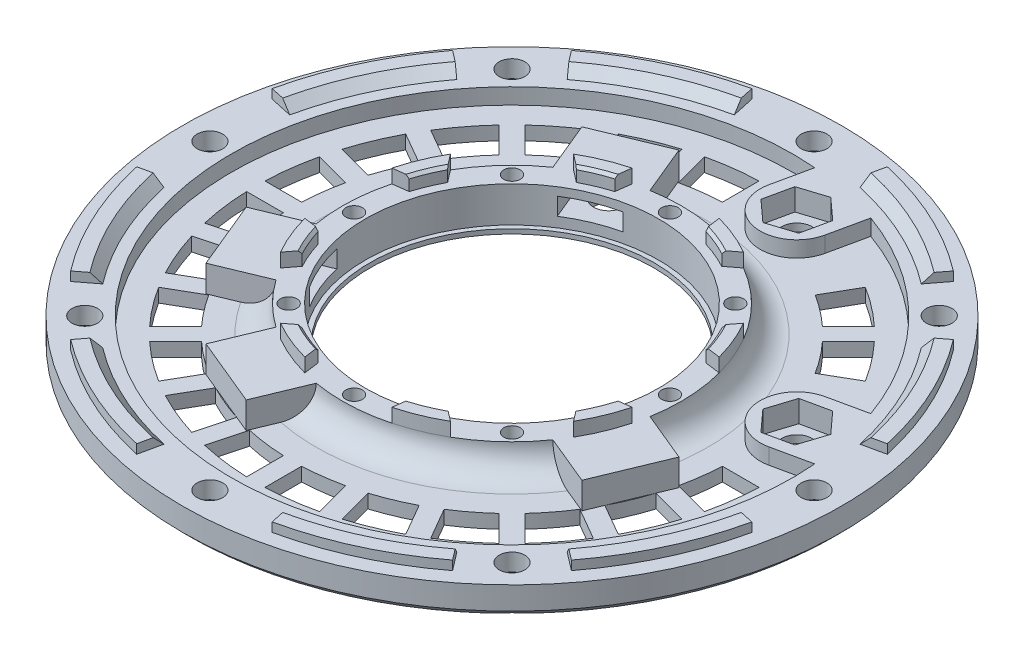
SolidWorks part; units mm, degrees
ref_plane "Front Plane" through (0, 0, 0) normal (0, 0, 1) x (1, 0, 0)
ref_plane "Top Plane" through (0, 0, 0) normal (0, 1, 0) x (1, 0, 0)
ref_plane "Right Plane" through (0, 0, 0) normal (1, 0, 0) x (0, 0, -1)
sketch "Sketch1" plane through (0, 0, 0) normal (0, 1, 0) x (1, 0, 0)
  circle A0 centre (0, 0) radius 16.025
  circle A1 centre (0, 0) radius 36
  dimension "D1" = 32.05
  dimension "D2" = 72
extrude "Boss-Extrude1" add sketch "Sketch1" along normal blind 1
sketch "Sketch2" plane through (0, 0, 0) normal (0, -1, 0) x (1, 0, 0)
  circle A0 centre (0, 0) radius 17.25 construction
  circle A1 centre (0, 0) radius 18.5 construction
  circle A2 centre (0, 0) radius 18.5
  circle A3 centre (0, 0) radius 16.025 construction
  circle A4 centre (0, 0) radius 16.025
  arc A5 (-1.2, 18.461) -> (-4.705, 17.8917) centre (0, 0) ccw construction
  point P3 (0, -17.25)
extrude "Boss-Extrude2" add sketch "Sketch2" against normal offset from surface (3.9 mm away) 3.9 up to face at (0, 0, 36)
fillet "Fillet1" radius 2.9 1 edges at (0, 1, 18.5)
sketch "Sketch4" plane through (0, 0, 0) normal (0, 1, 0) x (1, 0, 0)
  circle A0 centre (0, 0) radius 15.525
  circle A1 centre (0, 0) radius 36
  circle A2 centre (0, 0) radius 36
  circle A3 centre (0, 0) radius 16.025 construction
  dimension "D2" = 0.5
  dimension "D1" = 0
extrude "Boss-Extrude3" add sketch "Sketch4" against normal blind 0.5
sketch "Sketch5" plane through (0, 1, 0) normal (0, 1, 0) x (1, 0, 0)
  line L0 (27.99, -0.75) -> (19.9859, -0.75) construction
  line L1 (19.9859, 0.75) -> (27.99, 0.75) construction
  line L2 (27.99, -0.75) -> (19.9859, -0.75) construction
  line L3 (19.9859, 0.75) -> (27.99, 0.75) construction
  line L4 (0, 0) -> (36, 0) construction
  line L5 (0, 0) -> (34.7733, 9.3175) construction
  line L6 (34.7733, 9.3175) -> (36, 0) construction
  line L7 (0, 0) -> (35.3867, 4.6587) construction
  line L8 (27.99, 1) -> (23.9792, 1)
  line L9 (27.295, 6.2784) -> (23.4209, 5.2403)
  line L10 (27.99, -1) -> (23.9792, -1)
  line L11 (27.295, -6.2784) -> (23.4209, -5.2403)
  line L12 (26.7774, -8.2103) -> (22.9033, -7.1722)
  line L13 (24.74, -13.129) -> (21.2666, -11.1236)
  line L14 (23.74, -14.861) -> (20.2666, -12.8556)
  line L15 (20.499, -19.0848) -> (17.6629, -16.2487)
  line L16 (19.0848, -20.499) -> (16.2487, -17.6629)
  line L17 (14.861, -23.74) -> (12.8556, -20.2666)
  line L18 (13.129, -24.74) -> (11.1236, -21.2666)
  line L19 (8.2103, -26.7774) -> (7.1722, -22.9033)
  line L20 (6.2784, -27.295) -> (5.2403, -23.4209)
  line L21 (1, -27.99) -> (1, -23.9792)
  line L22 (-1, -27.99) -> (-1, -23.9792)
  line L23 (-6.2784, -27.295) -> (-5.2403, -23.4209)
  line L24 (-8.2103, -26.7774) -> (-7.1722, -22.9033)
  line L25 (-13.129, -24.74) -> (-11.1236, -21.2666)
  line L26 (-14.861, -23.74) -> (-12.8556, -20.2666)
  line L27 (-19.0848, -20.499) -> (-16.2487, -17.6629)
  line L28 (-20.499, -19.0848) -> (-17.6629, -16.2487)
  line L29 (-23.74, -14.861) -> (-20.2666, -12.8556)
  line L30 (-24.74, -13.129) -> (-21.2666, -11.1236)
  line L31 (-26.7774, -8.2103) -> (-22.9033, -7.1722)
  line L32 (-27.295, -6.2784) -> (-23.4209, -5.2403)
  line L33 (-27.99, -1) -> (-23.9792, -1)
  line L34 (-27.99, 1) -> (-23.9792, 1)
  line L35 (-27.295, 6.2784) -> (-23.4209, 5.2403)
  line L36 (-26.7774, 8.2103) -> (-22.9033, 7.1722)
  line L37 (-24.74, 13.129) -> (-21.2666, 11.1236)
  line L38 (-23.74, 14.861) -> (-20.2666, 12.8556)
  line L39 (-20.499, 19.0848) -> (-17.6629, 16.2487)
  line L40 (-19.0848, 20.499) -> (-16.2487, 17.6629)
  line L41 (-14.861, 23.74) -> (-12.8556, 20.2666)
  line L42 (-13.129, 24.74) -> (-11.1236, 21.2666)
  line L43 (-8.2103, 26.7774) -> (-7.1722, 22.9033)
  line L44 (-6.2784, 27.295) -> (-5.2403, 23.4209)
  line L45 (-1, 27.99) -> (-1, 23.9792)
  line L46 (1, 27.99) -> (1, 23.9792)
  line L47 (6.2784, 27.295) -> (5.2403, 23.4209)
  line L48 (8.2103, 26.7774) -> (7.1722, 22.9033)
  line L49 (13.129, 24.74) -> (11.1236, 21.2666)
  line L50 (14.861, 23.74) -> (12.8556, 20.2666)
  line L51 (19.0848, 20.499) -> (16.2487, 17.6629)
  line L52 (20.499, 19.0848) -> (17.6629, 16.2487)
  line L53 (23.74, 14.861) -> (20.2666, 12.8556)
  line L54 (24.74, 13.129) -> (21.2666, 11.1236)
  line L55 (26.7774, 8.2103) -> (22.9033, 7.1722)
  line L56 (0, 0) -> (23.9792, 1) construction
  circle A0 centre (0, 0) radius 24 construction
  circle A2 centre (0, 0) radius 36 construction
  arc A3 (23.9792, 1) -> (23.4209, 5.2403) centre (0, 0) ccw
  arc A4 (27.99, 1) -> (27.295, 6.2784) centre (0, 0) ccw
  arc A5 (27.295, -6.2784) -> (27.99, -1) centre (0, 0) ccw
  arc A6 (23.4209, -5.2403) -> (23.9792, -1) centre (0, 0) ccw
  arc A7 (24.74, -13.129) -> (26.7774, -8.2103) centre (0, 0) ccw
  arc A8 (21.2666, -11.1236) -> (22.9033, -7.1722) centre (0, 0) ccw
  arc A9 (20.499, -19.0848) -> (23.74, -14.861) centre (0, 0) ccw
  arc A10 (17.6629, -16.2487) -> (20.2666, -12.8556) centre (0, 0) ccw
  arc A11 (14.861, -23.74) -> (19.0848, -20.499) centre (0, 0) ccw
  arc A12 (12.8556, -20.2666) -> (16.2487, -17.6629) centre (0, 0) ccw
  arc A13 (8.2103, -26.7774) -> (13.129, -24.74) centre (0, 0) ccw
  arc A14 (7.1722, -22.9033) -> (11.1236, -21.2666) centre (0, 0) ccw
  arc A15 (1, -27.99) -> (6.2784, -27.295) centre (0, 0) ccw
  arc A16 (1, -23.9792) -> (5.2403, -23.4209) centre (0, 0) ccw
  arc A17 (-6.2784, -27.295) -> (-1, -27.99) centre (0, 0) ccw
  arc A18 (-5.2403, -23.4209) -> (-1, -23.9792) centre (0, 0) ccw
  arc A19 (-13.129, -24.74) -> (-8.2103, -26.7774) centre (0, 0) ccw
  arc A20 (-11.1236, -21.2666) -> (-7.1722, -22.9033) centre (0, 0) ccw
  arc A21 (-19.0848, -20.499) -> (-14.861, -23.74) centre (0, 0) ccw
  arc A22 (-16.2487, -17.6629) -> (-12.8556, -20.2666) centre (0, 0) ccw
  arc A23 (-23.74, -14.861) -> (-20.499, -19.0848) centre (0, 0) ccw
  arc A24 (-20.2666, -12.8556) -> (-17.6629, -16.2487) centre (0, 0) ccw
  arc A25 (-26.7774, -8.2103) -> (-24.74, -13.129) centre (0, 0) ccw
  arc A26 (-22.9033, -7.1722) -> (-21.2666, -11.1236) centre (0, 0) ccw
  arc A27 (-27.99, -1) -> (-27.295, -6.2784) centre (0, 0) ccw
  arc A28 (-23.9792, -1) -> (-23.4209, -5.2403) centre (0, 0) ccw
  arc A29 (-27.295, 6.2784) -> (-27.99, 1) centre (0, 0) ccw
  arc A30 (-23.4209, 5.2403) -> (-23.9792, 1) centre (0, 0) ccw
  arc A31 (-24.74, 13.129) -> (-26.7774, 8.2103) centre (0, 0) ccw
  arc A32 (-21.2666, 11.1236) -> (-22.9033, 7.1722) centre (0, 0) ccw
  arc A33 (-20.499, 19.0848) -> (-23.74, 14.861) centre (0, 0) ccw
  arc A34 (-17.6629, 16.2487) -> (-20.2666, 12.8556) centre (0, 0) ccw
  arc A35 (-14.861, 23.74) -> (-19.0848, 20.499) centre (0, 0) ccw
  arc A36 (-12.8556, 20.2666) -> (-16.2487, 17.6629) centre (0, 0) ccw
  arc A37 (-8.2103, 26.7774) -> (-13.129, 24.74) centre (0, 0) ccw
  arc A38 (-7.1722, 22.9033) -> (-11.1236, 21.2666) centre (0, 0) ccw
  arc A39 (-1, 27.99) -> (-6.2784, 27.295) centre (0, 0) ccw
  arc A40 (-1, 23.9792) -> (-5.2403, 23.4209) centre (0, 0) ccw
  arc A41 (6.2784, 27.295) -> (1, 27.99) centre (0, 0) ccw
  arc A42 (5.2403, 23.4209) -> (1, 23.9792) centre (0, 0) ccw
  arc A43 (13.129, 24.74) -> (8.2103, 26.7774) centre (0, 0) ccw
  arc A44 (11.1236, 21.2666) -> (7.1722, 22.9033) centre (0, 0) ccw
  arc A45 (19.0848, 20.499) -> (14.861, 23.74) centre (0, 0) ccw
  arc A46 (16.2487, 17.6629) -> (12.8556, 20.2666) centre (0, 0) ccw
  arc A47 (23.74, 14.861) -> (20.499, 19.0848) centre (0, 0) ccw
  arc A48 (20.2666, 12.8556) -> (17.6629, 16.2487) centre (0, 0) ccw
  arc A49 (26.7774, 8.2103) -> (24.74, 13.129) centre (0, 0) ccw
  arc A50 (22.9033, 7.1722) -> (21.2666, 11.1236) centre (0, 0) ccw
  dimension "D1" = 15
  dimension "D2" = 1
  dimension "D4" = 24
  dimension "D3" = 24
extrude "Cut-Extrude1" cut sketch "Sketch5" against normal through all both and the other way through all
sketch "Sketch7" plane through (0, 3.9, 0) normal (0, 1, 0) x (1, 0, 0)
  line L0 (0, 0) -> (0, 17.25) construction
  circle A0 centre (0, 17.25) radius 0.9
  circle A1 centre (12.1976, 12.1976) radius 0.9
  circle A2 centre (17.25, 0) radius 0.9
  circle A3 centre (12.1976, -12.1976) radius 0.9
  circle A4 centre (0, -17.25) radius 0.9
  circle A5 centre (-12.1976, -12.1976) radius 0.9
  circle A6 centre (-17.25, 0) radius 0.9
  circle A7 centre (-12.1976, 12.1976) radius 0.9
  point P21 (0, 0)
  dimension "D1" = 1.8
  dimension "D2" = 8
extrude "Cut-Extrude2" cut sketch "Sketch7" against normal through all
sketch "Sketch8" plane through (0, 1, 0) normal (0, 1, 0) x (1, 0, 0)
  arc A0 (-30.6392, -0.8144) -> (-29.9521, -6.5032) centre (0, 0) ccw construction
  arc A1 (-30.6392, -0.8144) -> (-29.9521, -6.5032) centre (0, 0) ccw construction
  arc A2 (-29.9521, 6.5032) -> (-30.6392, 0.8144) centre (0, 0) ccw construction
  arc A3 (-29.9521, 6.5032) -> (-30.6392, 0.8144) centre (0, 0) ccw construction
  circle A5 centre (0, 0) radius 30.65
  circle A6 centre (0, 0) radius 36 construction
  circle A7 centre (0, 0) radius 36
extrude "Boss-Extrude4" add sketch "Sketch8" along normal blind 1.7378
sketch "Sketch9" plane through (0, 2.7378, 0) normal (0, 1, 0) x (1, 0, 0)
  line L0 (0, 0) -> (-29.9521, 6.5032) construction
  line L1 (0, 0) -> (-29.9521, -6.5032) construction
  line L2 (-29.9521, 6.5032) -> (-29.9521, -6.5032) construction
  line L3 (-27.3707, 21.0023) -> (-23.9196, 18.3542) construction
  line L4 (0, 0) -> (0, 36) construction
  line L5 (0, 0) -> (-25.4558, 25.4558) construction
  line L6 (-24.3163, 18.6585) -> (0, 0) construction
  line L7 (-24.3163, 18.6585) -> (-28.5607, 21.9154) construction
  line L8 (-29.9521, 6.5032) -> (-35.1803, 7.6384) construction
  line L9 (-27.3521, 20.862) -> (-25.3687, 19.3401)
  line L10 (-31.2086, 14.47) -> (0, 0) construction
  line L11 (-33.5954, 7.3966) -> (-31.1523, 6.8662)
  line L12 (-7.3966, 33.5954) -> (-6.8662, 31.1523)
  line L13 (-20.862, 27.3521) -> (-19.3401, 25.3687)
  arc A0 (-29.9521, 6.5032) -> (-24.3163, 18.6585) centre (0, 0) cw construction
  arc A1 (-35.1803, 7.6384) -> (-28.5607, 21.9154) centre (0, 0) cw construction
  circle A2 centre (0, 0) radius 36 construction
  circle A3 centre (0, 0) radius 30.65 construction
  arc A4 (-27.2914, 20.9414) -> (-33.6168, 7.2989) centre (0, 0) ccw construction
  arc A5 (-31.1523, 6.8662) -> (-25.3687, 19.3401) centre (0, 0) cw
  arc A6 (-33.5954, 7.3966) -> (-27.3521, 20.862) centre (0, 0) cw
  circle A7 centre (0, 0) radius 36 construction
  arc A8 (-6.8662, 31.1523) -> (-19.3401, 25.3687) centre (0, 0) ccw
  arc A9 (-7.3966, 33.5954) -> (-20.862, 27.3521) centre (0, 0) ccw
  dimension "D2" = 0.1
  dimension "D3" = 45
  dimension "D4" = 0.1
  dimension "D1" = 2.5
extrude "Boss-Extrude5" add sketch "Sketch9" along normal blind 1
ref_axis "Axis1" through (0, -0.72, 0) along (0, 1, 0)
pattern_circular "CirPattern1" count 4 over 360 about axis through (0, -0.72, 0) along (0, 1, 0) of "Boss-Extrude5"
chamfer "Chamfer1" distance 1 angle 45 8 edges at (-28.9406, 3.7378, -13.4184) (-13.4184, 3.7378, -28.9406) (13.4184, 3.7378, -28.9406) (28.9406, 3.7378, -13.4184) (28.9406, 3.7378, 13.4184) (13.4184, 3.7378, 28.9406) (-13.4184, 3.7378, 28.9406) (-28.9406, 3.7378, 13.4184)
sketch "Sketch10" plane through (0, 2.7378, 0) normal (0, 1, 0) x (1, 0, 0)
  line L0 (0, 0) -> (0, 36) construction
  circle A0 centre (0, 0) radius 36 construction
  circle A1 centre (0, 33) radius 1.4 construction
  circle A2 centre (0, 33) radius 1.4
  circle A3 centre (23.3345, 23.3345) radius 1.4
  circle A4 centre (33, 0) radius 1.4
  circle A5 centre (23.3345, -23.3345) radius 1.4
  circle A6 centre (0, -33) radius 1.4
  circle A7 centre (-23.3345, -23.3345) radius 1.4
  circle A8 centre (-33, 0) radius 1.4
  circle A9 centre (-23.3345, 23.3345) radius 1.4
  point P26 (0, 0)
  dimension "D1" = 8
extrude "Cut-Extrude3" cut sketch "Sketch10" against normal through all both and the other way through all
chamfer "Chamfer2" distance 0.75 angle 45 1 edges at (0, -0.5, 36)
hole_wizard "CSK for M2.5 Flat Head Machine Screw1" positions "Sketch11" profile "Sketch12" countersink size "M2.5" standard "ANSI Metric" end condition through all
sketch "Sketch11" plane through (0, -0.5, 0) normal (0, -1, 0) x (-1, 0, 0)
  point P0 (0, -33)
  point P3 (23.3345, -23.3345)
  point P6 (33, 0)
  point P9 (23.3345, 23.3345)
  point P12 (0, 33)
  point P15 (-23.3345, 23.3345)
  point P18 (-33, 0)
  point P21 (-23.3345, -23.3345)
sketch "Sketch12" plane through (0, -0.5, 33) normal (1, 0, 0) x (0, 0, -1)
  line L0 (0, 0) -> (0, 4.4)
  line L1 (0, 4.4) -> (1.35, 4.4)
  line L2 (1.35, 4.4) -> (1.35, 1.4)
  line L3 (1.35, 1.4) -> (2.75, 0)
  line L5 (2.75, 0) -> (0, 0)
  line L6 (-1.35, 1.4) -> (-2.75, 0) construction
  line L11 (0, -6.35) -> (0, 107.95) construction
  dimension "Thru Hole Dia." = 2.7
  dimension "Thru Hole Depth" = 4.4
  dimension "Near C'Sink Dia." = 5.5
  dimension "Near C'Sink Angle" = 90
sketch "Sketch13" plane through (0, 3.9, 0) normal (0, 1, 0) x (1, 0, 0)
  line L0 (0, 0) -> (-7.0796, 17.0918) construction
  line L1 (0, 0) -> (0, 18.5) construction
  line L2 (-9.2808, 16.0037) -> (-7.9403, 14.9751)
  line L3 (-4.7538, 17.8788) -> (-4.9743, 16.2037)
  line L4 (4.7538, 17.8788) -> (4.9743, 16.2037)
  line L5 (9.2808, 16.0037) -> (7.9403, 14.9751)
  line L6 (16.0037, 9.2808) -> (14.9751, 7.9403)
  line L7 (17.8788, 4.7538) -> (16.2037, 4.9743)
  line L8 (17.8788, -4.7538) -> (16.2037, -4.9743)
  line L9 (16.0037, -9.2808) -> (14.9751, -7.9403)
  line L10 (9.2808, -16.0037) -> (7.9403, -14.9751)
  line L11 (4.7538, -17.8788) -> (4.9743, -16.2037)
  line L12 (-4.7538, -17.8788) -> (-4.9743, -16.2037)
  line L13 (-9.2808, -16.0037) -> (-7.9403, -14.9751)
  line L14 (-16.0037, -9.2808) -> (-14.9751, -7.9403)
  line L15 (-17.8788, -4.7538) -> (-16.2037, -4.9743)
  line L16 (-17.8788, 4.7538) -> (-16.2037, 4.9743)
  line L17 (-16.0037, 9.2808) -> (-14.9751, 7.9403)
  circle A0 centre (0, 0) radius 18.5 construction
  arc A1 (-7.9403, 14.9751) -> (-4.9743, 16.2037) centre (0, 0) cw
  arc A2 (-9.2808, 16.0037) -> (-4.7538, 17.8788) centre (0, 0) cw
  arc A3 (4.9743, 16.2037) -> (7.9403, 14.9751) centre (0, 0) cw
  arc A4 (4.7538, 17.8788) -> (9.2808, 16.0037) centre (0, 0) cw
  arc A5 (14.9751, 7.9403) -> (16.2037, 4.9743) centre (0, 0) cw
  arc A6 (16.0037, 9.2808) -> (17.8788, 4.7538) centre (0, 0) cw
  arc A7 (16.2037, -4.9743) -> (14.9751, -7.9403) centre (0, 0) cw
  arc A8 (17.8788, -4.7538) -> (16.0037, -9.2808) centre (0, 0) cw
  arc A9 (7.9403, -14.9751) -> (4.9743, -16.2037) centre (0, 0) cw
  arc A10 (9.2808, -16.0037) -> (4.7538, -17.8788) centre (0, 0) cw
  arc A11 (-4.9743, -16.2037) -> (-7.9403, -14.9751) centre (0, 0) cw
  arc A12 (-4.7538, -17.8788) -> (-9.2808, -16.0037) centre (0, 0) cw
  arc A13 (-14.9751, -7.9403) -> (-16.2037, -4.9743) centre (0, 0) cw
  arc A14 (-16.0037, -9.2808) -> (-17.8788, -4.7538) centre (0, 0) cw
  arc A15 (-16.2037, 4.9743) -> (-14.9751, 7.9403) centre (0, 0) cw
  arc A16 (-17.8788, 4.7538) -> (-16.0037, 9.2808) centre (0, 0) cw
  point P12 (-6.4865, 15.6598)
  point P20 (6.4865, 15.6598)
  point P25 (15.6598, 6.4865)
  point P30 (15.6598, -6.4865)
  point P35 (6.4865, -15.6598)
  point P40 (-6.4865, -15.6598)
  point P45 (-15.6598, -6.4865)
  point P50 (-15.6598, 6.4865)
  point P51 (0, 0)
  dimension "D1" = 22.5
  dimension "D2" = 30
  dimension "D3" = 1.55
  dimension "D4" = 4.9
  dimension "D5" = 8
extrude "Boss-Extrude6" add sketch "Sketch13" along normal blind 1.5
chamfer "Chamfer3" distance 0.3 angle 45 8 edges at (-15.6598, 5.4, -6.4865) (-15.6598, 5.4, 6.4865) (-6.4865, 5.4, 15.6598) (6.4865, 5.4, 15.6598) (15.6598, 5.4, 6.4865) (15.6598, 5.4, -6.4865) (6.4865, 5.4, -15.6598) (-6.4865, 5.4, -15.6598)
sketch "Sketch14" plane through (0, -0.5, 0) normal (0, -1, 0) x (1, 0, 0)
  line L0 (0, 0) -> (25.4558, -25.4558) construction
  line L1 (0, 0) -> (0, -36) construction
  line L6 (0, 0) -> (-22.1731, 9.1844) construction
  line L7 (0, 0) -> (-9.1844, -22.1731) construction
  circle A0 centre (0, 0) radius 36 construction
  arc A5 (-21.2666, 11.1236) -> (-22.9033, 7.1722) centre (0, 0) ccw construction
  circle A6 centre (-18.0157, 7.4623) radius 1.65
  circle A7 centre (-18.0157, 7.4623) radius 4.5 construction
  arc A8 (-11.1236, -21.2666) -> (-7.1722, -22.9033) centre (0, 0) ccw construction
  circle A9 centre (-7.4623, -18.0157) radius 1.65
  circle A10 centre (-7.4623, -18.0157) radius 4.5 construction
  circle A11 centre (18.0157, 7.4623) radius 1.65
  circle A12 centre (-7.4623, 18.0157) radius 1.65
  dimension "D2" = 3.3
  dimension "D3" = 9
  dimension "D1" = 45
sketch "Sketch15" plane through (0, 1, 0) normal (0, 1, 0) x (1, 0, 0)
  line L0 (-9.8825, 13.2519) -> (-12.8979, 20.5316)
  line L1 (-9.8825, 13.2519) -> (-2.3825, 16.3585)
  line L2 (-12.8979, 20.5316) -> (-5.3979, 23.6382)
  line L3 (-2.3825, 16.3585) -> (-5.3979, 23.6382)
  line L4 (-9.8825, 13.2519) -> (-5.3979, 23.6382) construction
  line L5 (-12.8979, 20.5316) -> (-2.3825, 16.3585) construction
  line L6 (0, 0) -> (-9.1844, 22.1731) construction
  line L7 (2.3825, 16.3585) -> (5.3979, 23.6382) [skipped]
  line L8 (2.3825, 16.3585) -> (9.8825, 13.2519) [skipped]
  line L9 (5.3979, 23.6382) -> (12.8979, 20.5316) [skipped]
  line L10 (9.8825, 13.2519) -> (12.8979, 20.5316) [skipped]
  line L11 (2.3825, 16.3585) -> (12.8979, 20.5316) construction
  line L12 (5.3979, 23.6382) -> (9.8825, 13.2519) construction
  line L13 (13.2519, 9.8825) -> (20.5316, 12.8979) [skipped]
  line L14 (13.2519, 9.8825) -> (16.3585, 2.3825) [skipped]
  line L15 (20.5316, 12.8979) -> (23.6382, 5.3979) [skipped]
  line L16 (16.3585, 2.3825) -> (23.6382, 5.3979) [skipped]
  line L17 (13.2519, 9.8825) -> (23.6382, 5.3979) construction
  line L18 (20.5316, 12.8979) -> (16.3585, 2.3825) construction
  line L19 (16.3585, -2.3825) -> (23.6382, -5.3979)
  line L20 (16.3585, -2.3825) -> (13.2519, -9.8825)
  line L21 (23.6382, -5.3979) -> (20.5316, -12.8979)
  line L22 (13.2519, -9.8825) -> (20.5316, -12.8979)
  line L23 (16.3585, -2.3825) -> (20.5316, -12.8979) construction
  line L24 (23.6382, -5.3979) -> (13.2519, -9.8825) construction
  line L25 (9.8825, -13.2519) -> (12.8979, -20.5316) [skipped]
  line L26 (9.8825, -13.2519) -> (2.3825, -16.3585) [skipped]
  line L27 (12.8979, -20.5316) -> (5.3979, -23.6382) [skipped]
  line L28 (2.3825, -16.3585) -> (5.3979, -23.6382) [skipped]
  line L29 (9.8825, -13.2519) -> (5.3979, -23.6382) construction
  line L30 (12.8979, -20.5316) -> (2.3825, -16.3585) construction
  line L31 (-2.3825, -16.3585) -> (-5.3979, -23.6382)
  line L32 (-2.3825, -16.3585) -> (-9.8825, -13.2519)
  line L33 (-5.3979, -23.6382) -> (-12.8979, -20.5316)
  line L34 (-9.8825, -13.2519) -> (-12.8979, -20.5316)
  line L35 (-2.3825, -16.3585) -> (-12.8979, -20.5316) construction
  line L36 (-5.3979, -23.6382) -> (-9.8825, -13.2519) construction
  line L37 (-13.2519, -9.8825) -> (-20.5316, -12.8979)
  line L38 (-13.2519, -9.8825) -> (-16.3585, -2.3825)
  line L39 (-20.5316, -12.8979) -> (-23.6382, -5.3979)
  line L40 (-16.3585, -2.3825) -> (-23.6382, -5.3979)
  line L41 (-13.2519, -9.8825) -> (-23.6382, -5.3979) construction
  line L42 (-20.5316, -12.8979) -> (-16.3585, -2.3825) construction
  line L43 (-16.3585, 2.3825) -> (-23.6382, 5.3979) [skipped]
  line L44 (-16.3585, 2.3825) -> (-13.2519, 9.8825) [skipped]
  line L45 (-23.6382, 5.3979) -> (-20.5316, 12.8979) [skipped]
  line L46 (-13.2519, 9.8825) -> (-20.5316, 12.8979) [skipped]
  line L47 (-16.3585, 2.3825) -> (-20.5316, 12.8979) construction
  line L48 (-23.6382, 5.3979) -> (-13.2519, 9.8825) construction
  line L49 (0, 0) -> (-9.1844, 22.1731) construction
  arc A1 (-7.1722, 22.9033) -> (-11.1236, 21.2666) centre (0, 0) ccw construction
  circle A2 centre (0, 0) radius 16.025 construction
  point P1 (-7.6402, 18.445)
  point P9 (7.6402, 18.445)
  point P18 (18.445, 7.6402)
  point P23 (18.445, -7.6402)
  point P28 (7.6402, -18.445)
  point P33 (-7.6402, -18.445)
  point P38 (-18.445, -7.6402)
  point P43 (-18.445, 7.6402)
  point P48 (0, 0)
  dimension "D1" = 7.5
  dimension "D2" = 8
extrude "Boss-Extrude7" add sketch "Sketch15" along normal up to surface (2.9 mm away) up to face at (0, 3.9, -16.35)
extrude "Cut-Extrude4" cut sketch "Sketch14" against normal blind 3.5
sketch "Sketch16" plane through (0, -0.5, 0) normal (0, -1, 0) x (1, 0, 0)
  line L0 (0, 0) -> (23.3345, -23.3345) construction
  line L1 (9.8544, 8.0903) -> (22.8679, -7.7606) construction
  line L2 (0, 0) -> (0, -17.25) construction
  line L3 (0, 0) -> (9.8544, 8.0903) construction
  line L4 (19.1824, 8.6291) -> (13.9057, 13.9057) construction
  line L5 (0, 0) -> (13.9057, 13.9057) construction
  line L6 (25.573, -5.5397) -> (28.0479, -3.0648) construction
  line L7 (28.0479, -3.0648) -> (12.4915, 12.4915) construction
  circle A0 centre (0, 0) radius 12.75 construction
  circle A1 centre (25.573, -5.5397) radius 1.65
  circle A2 centre (25.573, -5.5397) radius 3.5 construction
  circle A3 centre (18.0157, 7.4623) radius 1.65 construction
  circle A4 centre (5.5397, -25.573) radius 1.65
  dimension "D1" = 25.5
  dimension "D2" = 3.3
  dimension "D3" = 7
  dimension "D4" = 2
  dimension "D5" = 22
sketch "Sketch17" plane through (0, -0.5, 0) normal (0, -1, 0) x (1, 0, 0)
  line L0 (24.74, -13.129) -> (21.2666, -11.1236) construction
  line L1 (24.74, -13.129) -> (21.2666, -11.1236)
  line L2 (0, 0) -> (12.1976, -12.1976) construction
  line L3 (13.129, -24.74) -> (11.1236, -21.2666)
  arc A0 (21.2666, -11.1236) -> (22.9033, -7.1722) centre (0, 0) ccw construction
  arc A1 (24.74, -13.129) -> (26.7774, -8.2103) centre (0, 0) ccw construction
  arc A4 (21.2666, -11.1236) -> (22.1079, -9.3403) centre (0, 0) ccw
  arc A5 (24.74, -13.129) -> (25.8946, -10.6727) centre (0, 0) ccw
  arc A8 (25.8946, -10.6727) -> (22.1079, -9.3403) centre (25.573, -5.5397) ccw
  arc A9 (10.6727, -25.8946) -> (9.3403, -22.1079) centre (5.5397, -25.573) cw
  arc A10 (13.129, -24.74) -> (10.6727, -25.8946) centre (0, 0) cw
  arc A11 (11.1236, -21.2666) -> (9.3403, -22.1079) centre (0, 0) cw
extrude "Boss-Extrude8" add sketch "Sketch17" against normal up to surface (1.5 mm away) up to face at (25.7264, 1, -3.3869)
sketch "Sketch18" plane through (0, 1, 0) normal (0, 1, 0) x (1, 0, 0)
  line L0 (0, 0) -> (25.573, 5.5397) construction
  line L1 (24.7261, 9.449) -> (28.8522, 10.3429)
  line L2 (26.4198, 1.6304) -> (30.5459, 2.5242)
  line L3 (0, 0) -> (23.3345, 23.3345) construction
  line L4 (9.449, 24.7261) -> (10.3429, 28.8522)
  line L5 (1.6304, 26.4198) -> (2.5242, 30.5459)
  arc A0 (24.7261, 9.449) -> (26.4198, 1.6304) centre (25.573, 5.5397) ccw
  circle A1 centre (0, 0) radius 30.65 construction
  circle A2 centre (0, 0) radius 30.65 construction
  arc A3 (30.5459, 2.5242) -> (28.8522, 10.3429) centre (0, 0) ccw
  arc A4 (2.5242, 30.5459) -> (10.3429, 28.8522) centre (0, 0) cw
  arc A5 (9.449, 24.7261) -> (1.6304, 26.4198) centre (5.5397, 25.573) cw
  dimension "D1" = 8
extrude "Boss-Extrude9" add sketch "Sketch18" along normal up to surface (1.7378 mm away) up to face at (0, 2.7378, -31.6)
extrude "Cut-Extrude5" cut sketch "Sketch16" against normal through all
sketch "Sketch19" plane through (0, 2.7378, 0) normal (0, 1, 0) x (1, 0, 0)
  line L0 (0, 0) -> (25.573, 5.5397) construction
  line L1 (28.62, 6.1998) -> (26.5249, 8.5085)
  line L2 (26.5249, 8.5085) -> (23.4778, 7.8485)
  line L3 (23.4778, 7.8485) -> (22.526, 4.8797)
  line L4 (22.526, 4.8797) -> (24.6211, 2.5709)
  line L5 (24.6211, 2.5709) -> (27.6681, 3.231)
  line L6 (27.6681, 3.231) -> (28.62, 6.1998)
  line L7 (0, 0) -> (23.3345, 23.3345) construction
  line L8 (3.231, 27.6681) -> (6.1998, 28.62)
  line L9 (2.5709, 24.6211) -> (3.231, 27.6681)
  line L10 (4.8797, 22.526) -> (2.5709, 24.6211)
  line L11 (7.8485, 23.4778) -> (4.8797, 22.526)
  line L12 (8.5085, 26.5249) -> (7.8485, 23.4778)
  line L13 (6.1998, 28.62) -> (8.5085, 26.5249)
  circle A0 centre (25.573, 5.5397) radius 2.7 construction
  dimension "D1" = 5.4
extrude "Cut-Extrude6" cut sketch "Sketch19" against normal blind 2.4
sketch "Sketch20" plane through (0, 3, 0) normal (0, -1, 0) x (1, 0, 0)
  line L0 (0, 0) -> (-18.0157, 7.4623) construction
  line L1 (-21.6087, 5.974) -> (-16.5274, 3.8693)
  line L2 (-21.6087, 5.974) -> (-19.5039, 11.0554)
  line L3 (-16.5274, 3.8693) -> (-14.4226, 8.9506) construction
  line L4 (-19.5039, 11.0554) -> (-14.4226, 8.9506)
  line L5 (-21.6087, 5.974) -> (-14.4226, 8.9506) construction
  line L6 (-16.5274, 3.8693) -> (-19.5039, 11.0554) construction
  line L7 (-14.4226, 8.9506) -> (-13.064, 8.3879)
  line L8 (-13.064, 8.3879) -> (-15.1688, 3.3065)
  line L9 (-15.1688, 3.3065) -> (-16.5274, 3.8693)
  line L10 (-8.3879, 13.064) -> (-8.9506, 14.4226)
  line L11 (-11.0554, 19.5039) -> (-8.9506, 14.4226)
  line L12 (-11.0554, 19.5039) -> (-5.974, 21.6087)
  line L13 (-5.974, 21.6087) -> (-3.8693, 16.5274)
  line L14 (-3.8693, 16.5274) -> (-3.3065, 15.1688)
  line L15 (-3.3065, 15.1688) -> (-8.3879, 13.064)
  line L16 (3.3065, 15.1688) -> (3.8693, 16.5274) [skipped]
  line L17 (5.974, 21.6087) -> (3.8693, 16.5274) [skipped]
  line L18 (5.974, 21.6087) -> (11.0554, 19.5039) [skipped]
  line L19 (11.0554, 19.5039) -> (8.9506, 14.4226) [skipped]
  line L20 (8.9506, 14.4226) -> (8.3879, 13.064) [skipped]
  line L21 (8.3879, 13.064) -> (3.3065, 15.1688) [skipped]
  line L22 (13.064, 8.3879) -> (14.4226, 8.9506)
  line L23 (19.5039, 11.0554) -> (14.4226, 8.9506)
  line L24 (19.5039, 11.0554) -> (21.6087, 5.974)
  line L25 (21.6087, 5.974) -> (16.5274, 3.8693)
  line L26 (16.5274, 3.8693) -> (15.1688, 3.3065)
  line L27 (15.1688, 3.3065) -> (13.064, 8.3879)
  line L28 (15.1688, -3.3065) -> (16.5274, -3.8693) [skipped]
  line L29 (21.6087, -5.974) -> (16.5274, -3.8693) [skipped]
  line L30 (21.6087, -5.974) -> (19.5039, -11.0554) [skipped]
  line L31 (19.5039, -11.0554) -> (14.4226, -8.9506) [skipped]
  line L32 (14.4226, -8.9506) -> (13.064, -8.3879) [skipped]
  line L33 (13.064, -8.3879) -> (15.1688, -3.3065) [skipped]
  line L34 (8.3879, -13.064) -> (8.9506, -14.4226) [skipped]
  line L35 (11.0554, -19.5039) -> (8.9506, -14.4226) [skipped]
  line L36 (11.0554, -19.5039) -> (5.974, -21.6087) [skipped]
  line L37 (5.974, -21.6087) -> (3.8693, -16.5274) [skipped]
  line L38 (3.8693, -16.5274) -> (3.3065, -15.1688) [skipped]
  line L39 (3.3065, -15.1688) -> (8.3879, -13.064) [skipped]
  line L40 (-3.3065, -15.1688) -> (-3.8693, -16.5274)
  line L41 (-5.974, -21.6087) -> (-3.8693, -16.5274)
  line L42 (-5.974, -21.6087) -> (-11.0554, -19.5039)
  line L43 (-11.0554, -19.5039) -> (-8.9506, -14.4226)
  line L44 (-8.9506, -14.4226) -> (-8.3879, -13.064)
  line L45 (-8.3879, -13.064) -> (-3.3065, -15.1688)
  line L46 (-13.064, -8.3879) -> (-14.4226, -8.9506) [skipped]
  line L47 (-19.5039, -11.0554) -> (-14.4226, -8.9506) [skipped]
  line L48 (-19.5039, -11.0554) -> (-21.6087, -5.974) [skipped]
  line L49 (-21.6087, -5.974) -> (-16.5274, -3.8693) [skipped]
  line L50 (-16.5274, -3.8693) -> (-15.1688, -3.3065) [skipped]
  line L51 (-15.1688, -3.3065) -> (-13.064, -8.3879) [skipped]
  circle A0 centre (0, 0) radius 15.525 construction
  point P57 (0, 0)
  dimension "D1" = 5.5
  dimension "D2" = 8
extrude "Cut-Extrude7" cut sketch "Sketch20" along normal blind 1.9
ref_plane "Plane1" through (0.6364, 0, 0.6364) normal (-0.7071, 0, -0.7071) x (-0.7071, 0, 0.7071)
